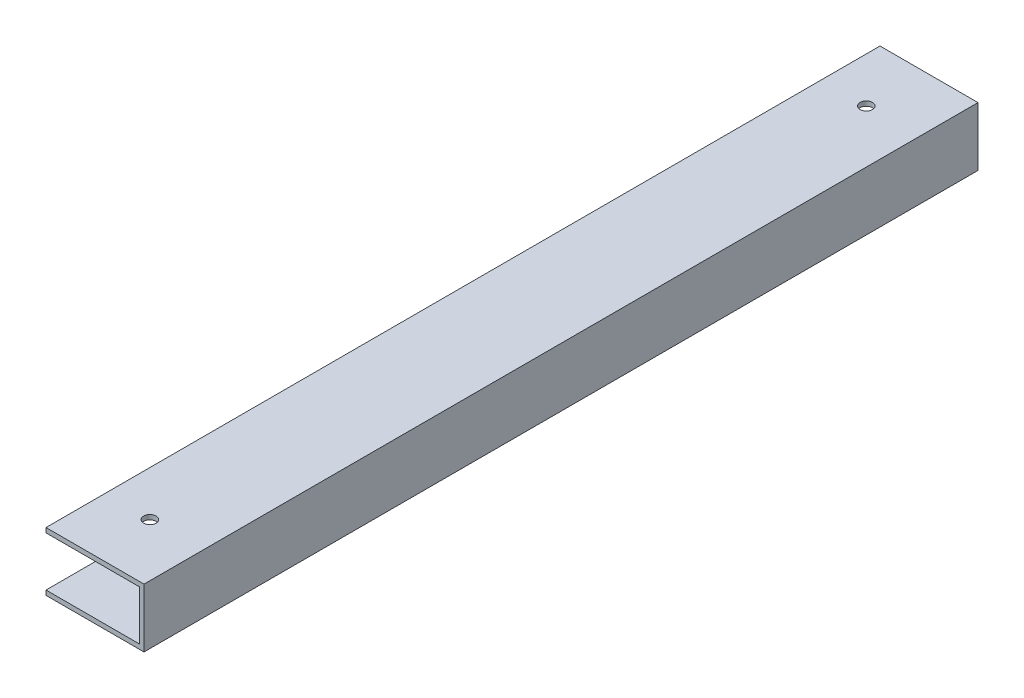
SolidWorks part; units mm, degrees
material "AISI 1020 Acero laminado en frío"
ref_plane "Alzado" through (0, 0, 0) normal (0, 0, 1) x (1, 0, 0)
ref_plane "Planta" through (0, 0, 0) normal (0, 1, 0) x (1, 0, 0)
ref_plane "Vista lateral" through (0, 0, 0) normal (1, 0, 0) x (0, 0, -1)
sketch "Croquis2" plane through (0, 0, 0) normal (0, 0, 1) x (1, 0, 0)
  line L1 (50, -30) -> (-50, -30)
  line L2 (50, -30) -> (50, 30)
  line L3 (50, 30) -> (-50, 30)
  line L4 (-50, -30) -> (-50, 30)
  line L5 (50, -30) -> (-50, 30) construction
  line L6 (50, 30) -> (-50, -30) construction
  point P0 (0, 0)
  point P6 (0, 30)
  dimension "D1" = 60
  dimension "D2" = 100
extrude "Saliente-Extruir1" add sketch "Croquis2" along normal mid plane 851
sketch "Croquis6" plane through (0, 0, 425.5) normal (0, 0, 1) x (1, 0, 0)
  line L4 (-50, 30) -> (-50, -30)
  line L5 (-50, -30) -> (50, -30)
  line L6 (50, -30) -> (50, 30)
  line L7 (50, 30) -> (-50, 30)
  line L8 (-50, 30) -> (-50, -30)
  line L9 (-50, -30) -> (50, -30)
  line L10 (50, -30) -> (50, 30)
  line L11 (50, 30) -> (-50, 30)
  line L16 (-45.2375, 25.2375) -> (-45.2375, -25.2375)
  line L17 (-45.2375, -25.2375) -> (45.2375, -25.2375)
  line L18 (45.2375, -25.2375) -> (45.2375, 25.2375)
  line L19 (45.2375, 25.2375) -> (-45.2375, 25.2375)
  line L20 (-45.2375, 25.2375) -> (-45.2375, -25.2375)
  line L21 (-45.2375, -25.2375) -> (45.2375, -25.2375)
  line L22 (45.2375, -25.2375) -> (45.2375, 25.2375)
  line L23 (45.2375, 25.2375) -> (-45.2375, 25.2375)
  dimension "D1" = 0
  dimension "D2" = 4.7625
extrude "Cortar-Extruir1" cut sketch "Croquis6" against normal blind 900 contours L22 L23 L20 L21 region at (0, 0, 425.5)
sketch "Croquis7" plane through (-50, 0, 0) normal (-1, 0, 0) x (0, 0, 1)
  line L0 (-425.5, 30) -> (-425.5, -30) construction
  line L1 (425.5, -25.2375) -> (-425.5, -25.2375)
  line L2 (425.5, -25.2375) -> (425.5, 25.2375)
  line L3 (425.5, 25.2375) -> (-425.5, 25.2375)
  line L4 (-425.5, -25.2375) -> (-425.5, 25.2375)
  line L5 (425.5, -25.2375) -> (-425.5, 25.2375) construction
  line L6 (425.5, 25.2375) -> (-425.5, -25.2375) construction
  line L7 (425.5, -30) -> (-425.5, -30) construction
  point P0 (0, 0)
  dimension "D1" = 4.7625
extrude "Cortar-Extruir2" cut sketch "Croquis7" against normal blind 20
sketch "Croquis8" plane through (0, 30, 0) normal (0, 1, 0) x (1, 0, 0)
  line L0 (-121.5247, 0) -> (93.3442, 0) construction
  line L1 (0, 497.4221) -> (0, -494.6167) construction
  line L4 (50, 425.5) -> (-50, 425.5) construction
  circle A0 centre (-4, 365.5) radius 6.35
  circle A1 centre (-4, -365.5) radius 6.35
  point P7 (0, 0)
  dimension "D1" = 12.7
  dimension "D2" = 60
  dimension "D3" = 4
extrude "Cortar-Extruir3" cut sketch "Croquis8" against normal blind 80
